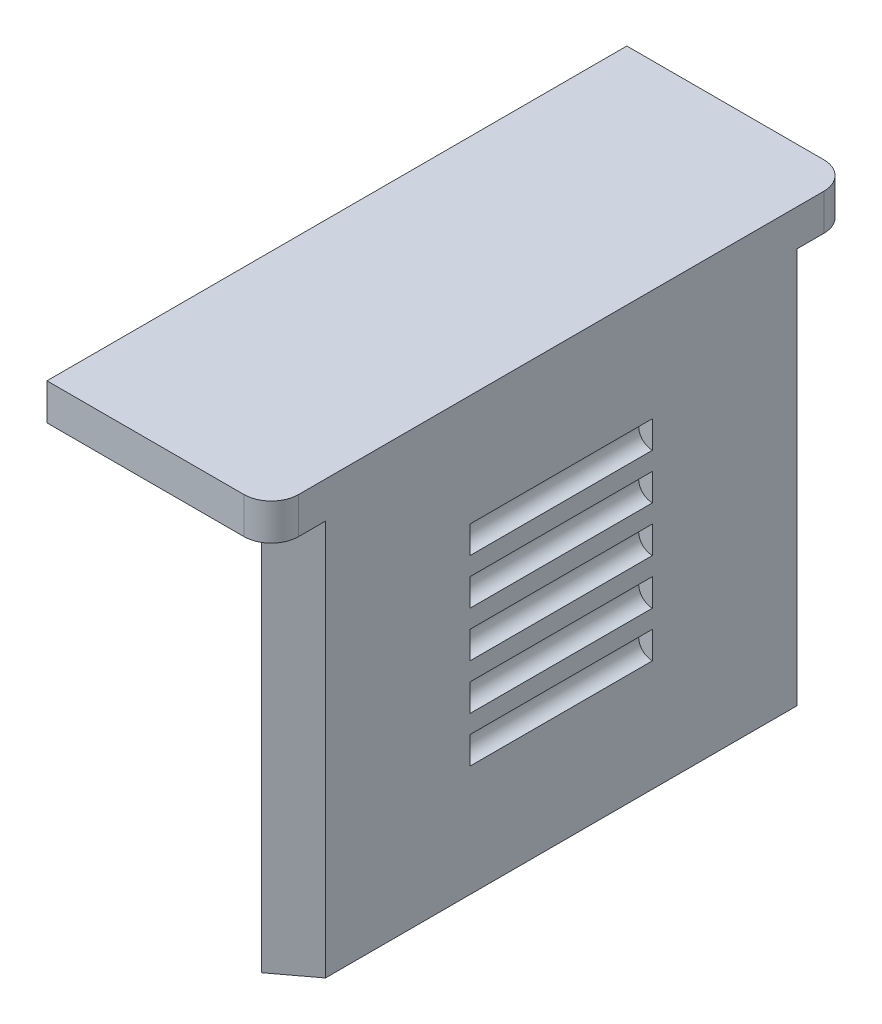
SolidWorks part; units mm, degrees
ref_plane "Alzado" through (0, 0, 0) normal (0, 0, 1) x (1, 0, 0)
ref_plane "Planta" through (0, 0, 0) normal (0, 1, 0) x (1, 0, 0)
ref_plane "Vista lateral" through (0, 0, 0) normal (1, 0, 0) x (0, 0, -1)
sketch "Croquis1" plane through (0, 111.4679, 0) normal (0, 1, 0) x (1, 0, 0)
  line L0 (-3.6522, -72.4184) -> (-15.9522, -72.4184)
  line L5 (-15.9522, -72.4184) -> (-15.9522, -104.2184)
  line L6 (-15.9522, -104.2184) -> (-3.6522, -104.2184)
  line L7 (-3.6522, -104.2184) -> (-3.6522, -72.4184)
  dimension "D1" = 12.3
  dimension "D2" = 31.8
extrude "Saliente-Extruir1" add sketch "Croquis1" against normal blind 2
sketch "Croquis2" plane through (0, 109.4679, 0) normal (0, -1, 0) x (1, 0, 0)
  line L0 (-3.6522, 101.2434) -> (-5.6522, 102.7434)
  line L3 (-3.6522, 104.2184) -> (-3.6522, 72.4184) construction
  line L4 (-15.9522, 88.3184) -> (1.8923, 88.3184) construction
  line L9 (-5.6522, 102.7434) -> (-5.6522, 73.8934)
  line L10 (-15.9522, 72.4184) -> (-15.9522, 104.2184) construction
  line L12 (-3.6522, 75.3934) -> (-3.6522, 101.2434)
  line L13 (-3.6522, 75.3934) -> (-5.6522, 73.8934)
  dimension "D1" = 53.13
  dimension "D2" = 2.5
  dimension "D3" = 28.85
extrude "Saliente-Extruir2" add sketch "Croquis2" along normal blind 21.7
ref_axis "Eje1" through (-3.6522, 111.4679, 88.3184) along (0, -1, 0)
ref_plane "Plano2" through (0, 0, 88.3184) normal (0, 0, 1) x (0, -1, 0)
sketch "Croquis4" plane through (0, 0, 88.3184) normal (0, 0, 1) x (0, -1, 0)
  line L0 (-104.6179, -3.6522) -> (-111.4679, -3.6522) construction
  line L1 (-111.4679, -3.6522) -> (-87.7679, -3.6522) construction
  line L2 (-94.6179, -3.6522) -> (-87.7679, -3.6522) construction
  circle A0 centre (-104.6179, -3.6522) radius 0.75
  circle A1 centre (-102.1179, -3.6522) radius 0.75
  circle A2 centre (-99.6179, -3.6522) radius 0.75
  circle A3 centre (-97.1179, -3.6522) radius 0.75
  circle A4 centre (-94.6179, -3.6522) radius 0.75
  dimension "D2" = 5
  dimension "D3" = 2.5
  dimension "D1" = 1.5
sketch "Croquis5" plane through (0, 109.4679, 0) normal (0, -1, 0) x (1, 0, 0)
  line L0 (-5.6522, 102.7434) -> (-5.6522, 73.8934) construction
  line L1 (-5.6522, 95.8184) -> (-6.6522, 95.8184)
  line L2 (-5.6522, 95.8184) -> (-5.6522, 80.8184)
  line L3 (-5.6522, 80.8184) -> (-6.6522, 80.8184)
  line L4 (-6.6522, 95.8184) -> (-6.6522, 80.8184)
  line L5 (-15.9522, 88.3184) -> (-5.6522, 88.3184) construction
  line L6 (-15.9522, 72.4184) -> (-15.9522, 104.2184) construction
  dimension "D1" = 15
  dimension "D2" = 1
extrude "Saliente-Extruir4" add sketch "Croquis5" along normal blind 20
extrude "Cortar-Extruir1" cut sketch "Croquis4" against normal mid plane 10
fillet "Redondeo1" radius 1.5 2 edges at (-3.6522, 110.4679, 72.4184) (-3.6522, 110.4679, 104.2184)
